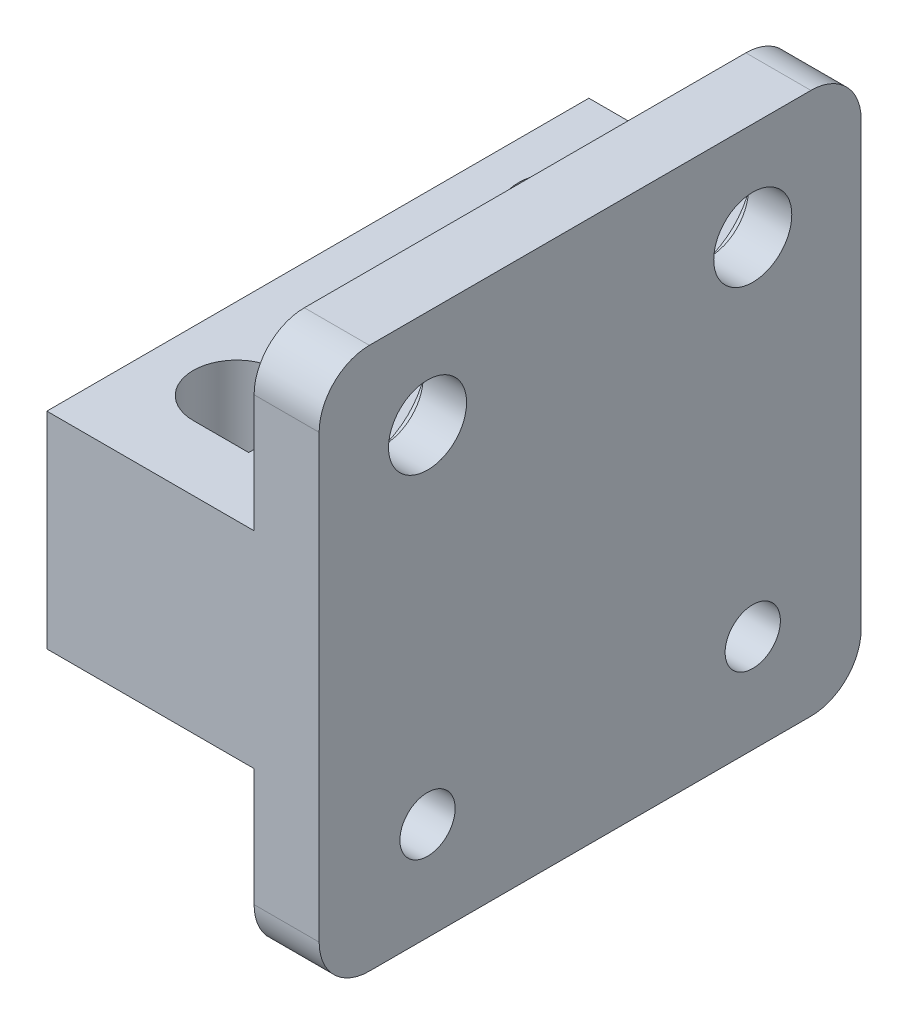
SolidWorks part; units mm, degrees
ref_plane "Front" through (0, 0, 0) normal (0, 0, 1) x (1, 0, 0)
ref_plane "Top" through (0, 0, 0) normal (0, 1, 0) x (1, 0, 0)
ref_plane "Right" through (0, 0, 0) normal (1, 0, 0) x (0, 0, -1)
sketch "Sketch2" plane through (0, 0, 0) normal (1, 0, 0) x (0, 0, -1)
  line L1 (-25, -25) -> (25, -25)
  line L2 (-25, -25) -> (-25, 25)
  line L3 (-25, 25) -> (25, 25)
  line L4 (25, -25) -> (25, 25)
  line L5 (0, 25) -> (0, -25) construction
  line L6 (-25, 0) -> (25, 0) construction
  point P0 (0, 0)
  dimension "D1" = 50
  dimension "D2" = 50
extrude "Boss-Extrude1" add sketch "Sketch2" along normal blind 6
sketch "Sketch3" plane through (25, 0, 0) normal (0, 1, 0) x (0, 0, 1)
  line L0 (-25, -19) -> (-25, -25) construction
  line L2 (25, -25) -> (-25, -25) construction
  line L3 (-25, -44.1188) -> (25, -44.1188)
  line L4 (-25, -44.1188) -> (-25, -25)
  line L5 (-19, -32.4282) -> (-19, -36.6188)
  line L6 (-25, -25) -> (25, -25)
  line L7 (25, -44.1188) -> (25, -25)
  line L8 (-15, -34.7376) -> (-11, -32.4282) construction
  line L9 (-11, -32.4282) -> (-11, -27.8094)
  line L10 (-11, -27.8094) -> (-15, -25.5)
  line L11 (-15, -25.5) -> (-19, -27.8094)
  line L12 (-19, -27.8094) -> (-19, -32.4282)
  line L13 (-19, -32.4282) -> (-15, -34.7376) construction
  line L14 (-11, -36.6188) -> (-11, -32.4282)
  line L15 (-15, -30.1188) -> (15, -30.1188) construction
  line L16 (19, -32.4282) -> (15, -34.7376) construction
  line L17 (15, -34.7376) -> (11, -32.4282) construction
  line L18 (11, -36.6188) -> (11, -32.4282)
  line L19 (19, -27.8094) -> (19, -32.4282)
  line L20 (15, -25.5) -> (19, -27.8094)
  line L21 (11, -27.8094) -> (15, -25.5)
  line L22 (11, -32.4282) -> (11, -27.8094)
  line L23 (19, -32.4282) -> (19, -36.6188)
  line L27 (0, -25) -> (0, -30.1188) construction
  circle A0 centre (-15, -30.1188) radius 4 construction
  arc A1 (-19, -36.6188) -> (-11, -36.6188) centre (-15, -36.6188) ccw
  circle A2 centre (15, -30.1188) radius 4 construction
  arc A3 (19, -36.6188) -> (11, -36.6188) centre (15, -36.6188) cw
  point P7 (0, -29.9555)
  point P10 (-13.9577, -43.9906)
  dimension "D1" = 30
  dimension "D2" = 3.5
  dimension "D4" = 8
  dimension "D3" = 0.5
  dimension "D5" = 6.5
extrude "Boss-Extrude2" add sketch "Sketch3" against normal mid plane 19
sketch "Sketch5" plane through (9.5, 9.5, 0) normal (0, -1, 0) x (0, 0, 1)
  line L0 (-19, 16) -> (-11, 16)
  line L1 (11, 16) -> (19, 16)
  line L4 (-11, 12.3094) -> (-11, 21.1188)
  line L5 (-15, 10) -> (-11, 12.3094)
  line L6 (-19, 12.3094) -> (-15, 10)
  line L7 (-19, 21.1188) -> (-19, 12.3094)
  line L8 (-11, 12.3094) -> (-11, 16)
  line L9 (-15, 10) -> (-11, 12.3094)
  line L10 (-19, 12.3094) -> (-15, 10)
  line L11 (-19, 16) -> (-19, 12.3094)
  line L12 (19, 12.3094) -> (19, 21.1188)
  line L13 (15, 10) -> (19, 12.3094)
  line L14 (11, 12.3094) -> (15, 10)
  line L15 (11, 21.1188) -> (11, 12.3094)
  line L16 (19, 12.3094) -> (19, 16)
  line L17 (15, 10) -> (19, 12.3094)
  line L18 (11, 12.3094) -> (15, 10)
  line L19 (11, 16) -> (11, 12.3094)
  arc A1 (-11, 21.1188) -> (-19, 21.1188) centre (-15, 21.1188) ccw
  arc A3 (19, 21.1188) -> (11, 21.1188) centre (15, 21.1188) ccw
  dimension "D3" = 6
  dimension "D1" = 0
  dimension "D2" = 0
extrude "Boss-Extrude3" add sketch "Sketch5" along normal blind 12
sketch "Sketch6" plane through (0, 0, 0) normal (1, 0, 0) x (0, 0, -1)
  line L1 (15, -15.95) -> (-15, -15.95) construction
  line L2 (15, -15.95) -> (15, 15.95) construction
  line L3 (15, 15.95) -> (-15, 15.95) construction
  line L4 (-15, -15.95) -> (-15, 15.95) construction
  line L5 (0, 15.95) -> (0, -15.95) construction
  line L6 (15, 0) -> (-15, 0) construction
  circle A0 centre (-15, 15.95) radius 3.6
  circle A1 centre (15, 15.95) radius 3.6
  circle A2 centre (-15, -15.95) radius 2.55
  circle A3 centre (15, -15.95) radius 2.55
  point P0 (0, 0)
  dimension "D3" = 7.2
  dimension "D4" = 5.1
  dimension "D1" = 31.9
  dimension "D2" = 30
extrude "Cut-Extrude2" cut sketch "Sketch6" along normal through all
sketch "Sketch7" plane through (0, 0, 0) normal (-1, 0, 0) x (0, 0, 1)
  circle A0 centre (-15, -15.95) radius 5.05
  circle A1 centre (15, -15.95) radius 5.05
  circle A2 centre (-15, 15.95) radius 6
  circle A3 centre (15, 15.95) radius 6
  dimension "D1" = 12
  dimension "D2" = 10.1
extrude "Cut-Extrude3" cut sketch "Sketch7" against normal blind 2
hole_wizard "M4x0.7 Tapped Hole1" positions "Sketch9" profile "Sketch10" tap size "M4x0.7" standard "ANSI Metric" end condition up to next
sketch "Sketch9" plane through (-19.1188, 0, 0) normal (1, 0, 0) x (0, -1, 0)
  line L0 (5.5, -15) -> (5.5, 15) construction
  line L3 (5.5, 0) -> (0, 0) construction
  line L6 (9.5, 25) -> (9.5, -25) construction
  point P0 (5.5, 15)
  point P2 (5.5, -15)
  point P15 (7.1041, 0)
  dimension "D1" = 30
  dimension "D2" = 4
sketch "Sketch10" plane through (-19.1188, -5.5, -15) normal (0, 1, 0) x (0, 0, 1)
  line L0 (0, 0) -> (0, 3.5)
  line L1 (0, 3.5) -> (1.65, 3.5)
  line L2 (1.65, 3.5) -> (1.65, 0)
  line L5 (1.65, 0) -> (0, 0)
  line L11 (0, -6.35) -> (0, 107.95) construction
  dimension "Thread Major Dia." = 3.3
  dimension "Thru Tap Drill Depth" = 3.5
hole_wizard "M4x0.7 Tapped Hole2" positions "Sketch11" profile "Sketch12" tap size "M4x0.7" standard "ANSI Metric"
sketch "Sketch11" plane through (-19.1188, 0, 0) normal (-1, 0, 0) x (0, 0, 1)
  line L0 (-9.525, 2.5) -> (9.525, 2.5) construction
  line L3 (0, 2.5) -> (0, 0) construction
  point P0 (-9.525, 2.5)
  point P2 (9.525, 2.5)
  point P15 (0, 2.4244)
  dimension "D1" = 19.05
  dimension "D2" = 2.5
sketch "Sketch12" plane through (-19.1188, 2.5, -9.525) normal (0, 1, 0) x (0, 0, 1)
  line L0 (0, 0) -> (0, 10.9914)
  line L1 (0, 10.9914) -> (1.65, 10)
  line L2 (1.65, 10) -> (1.65, 0)
  line L5 (1.65, 0) -> (0, 0)
  line L10 (0, 10.9914) -> (-1.65, 10) construction
  line L11 (0, -6.35) -> (0, 107.95) construction
  dimension "Tap Drill Dia." = 3.3
  dimension "Tap Drill Depth" = 10
  dimension "Drill Angle" = 118
cosmetic thread "Hole Thread1" parameters "D1"=8, "D2"=4
cosmetic thread "Hole Thread2" parameters "D1"=8, "D2"=4
fillet "Fillet1" radius 4.635 4 edges at (3, 25, 25) (3, 25, -25) (3, -25, -25) (3, -25, 25)
